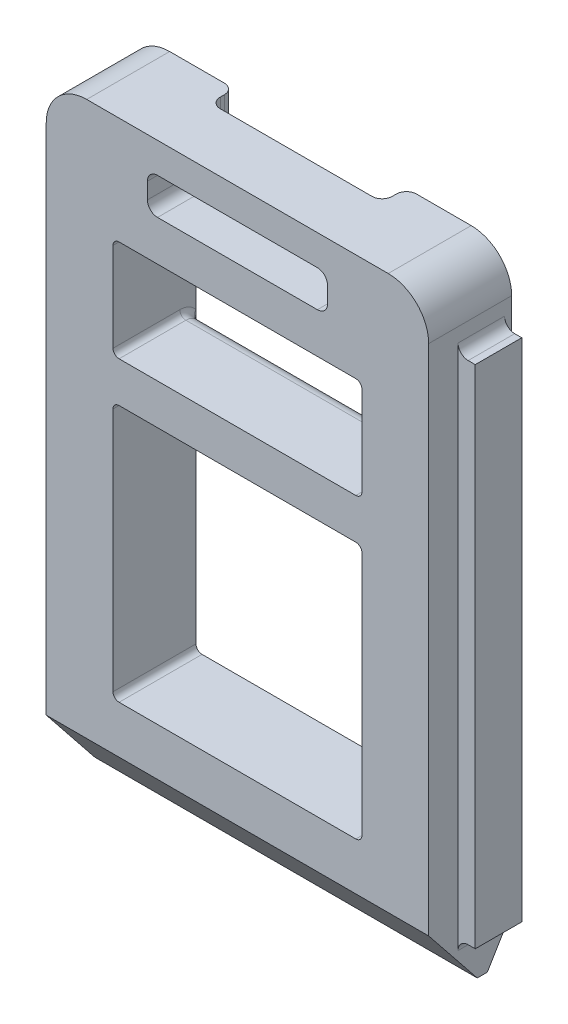
SolidWorks part; units mm, degrees
ref_plane "Front Plane" through (0, 0, 0) normal (0, 0, 1) x (1, 0, 0)
ref_plane "Top Plane" through (0, 0, 0) normal (0, 1, 0) x (1, 0, 0)
ref_plane "Right Plane" through (0, 0, 0) normal (1, 0, 0) x (0, 0, -1)
sketch "Sketch1" plane through (0, 0, 110.6411) normal (0, 0, 1) x (1, 0, 0)
  line L0 (16.3491, 91.493) -> (16.3491, 66.493) construction
  line L1 (16.1491, 94.693) -> (-2.7509, 94.693)
  line L2 (16.1491, 94.693) -> (16.1491, 64.343)
  line L3 (16.1491, 64.343) -> (-2.7509, 64.343)
  line L4 (-2.7509, 94.693) -> (-2.7509, 64.343)
  line L5 (-2.9509, 66.493) -> (-2.9509, 91.493) construction
  line L6 (16.3491, 91.493) -> (-2.9509, 91.493) construction
  line L7 (16.3491, 66.493) -> (18.9491, 66.493) construction
  dimension "D1" = 0.2
  dimension "D2" = 0.2
  dimension "D3" = 3.2
  dimension "D4" = 2.15
extrude "Boss-Extrude1" add sketch "Sketch1" along normal offset from surface (4.1 mm away) 0.5 from offset 0.4
sketch "Sketch2" plane through (0, 94.693, 0) normal (0, 1, 0) x (1, 0, 0)
  line L0 (-2.7509, -115.1411) -> (-2.7509, -111.0411) construction
  line L1 (16.1491, -115.1411) -> (16.1491, -111.0411) construction
  line L2 (-2.7509, -113.6911) -> (-2.7509, -111.3911)
  line L3 (16.1491, -113.6911) -> (16.1491, -111.3911)
  line L4 (-3.9509, -114.0411) -> (-2.9509, -114.0411) construction
  line L5 (-3.9509, -111.0411) -> (-3.9509, -114.0411) construction
  line L6 (-2.9509, -111.0411) -> (-3.9509, -111.0411) construction
  line L7 (17.3491, -111.0411) -> (16.3491, -111.0411) construction
  line L8 (17.3491, -114.0411) -> (17.3491, -111.0411) construction
  line L9 (16.3491, -114.0411) -> (17.3491, -114.0411) construction
  line L10 (-3.9509, -114.0411) -> (-2.9509, -114.0411) construction
  line L11 (-3.9509, -111.0411) -> (-3.9509, -114.0411) construction
  line L12 (-2.9509, -111.0411) -> (-3.9509, -111.0411) construction
  line L13 (17.3491, -111.0411) -> (16.3491, -111.0411) construction
  line L14 (17.3491, -114.0411) -> (17.3491, -111.0411) construction
  line L15 (16.3491, -114.0411) -> (17.3491, -114.0411) construction
  line L16 (16.1491, -113.6911) -> (16.9991, -113.6911)
  line L17 (16.9991, -113.6911) -> (16.9991, -111.3911)
  line L18 (16.9991, -111.3911) -> (16.1491, -111.3911)
  line L19 (-2.7509, -111.3911) -> (-3.6009, -111.3911)
  line L20 (-3.6009, -111.3911) -> (-3.6009, -113.6911)
  line L21 (-3.6009, -113.6911) -> (-2.7509, -113.6911)
  line L22 (16.3491, -113.6911) -> (16.9991, -113.6911) construction
  line L23 (16.9991, -111.3911) -> (16.3491, -111.3911) construction
  line L24 (-3.6009, -113.6911) -> (-2.9509, -113.6911) construction
  line L25 (-2.9509, -111.3911) -> (-3.6009, -111.3911) construction
  dimension "D1" = 0.35
extrude "Boss-Extrude2" add sketch "Sketch2" against normal up to surface (25 mm away) from surface at -3.2
fillet "Fillet3" radius 2 2 edges at (-2.7509, 94.693, 113.0911) (16.1491, 94.693, 113.0911)
sketch "Sketch3" plane through (0, 0, 115.1411) normal (0, 0, 1) x (1, 0, 0)
  line L0 (14.1491, 94.693) -> (-0.7509, 94.693) construction
  line L1 (11.1491, 93.193) -> (2.2491, 93.193)
  line L2 (11.1491, 93.193) -> (11.1491, 91.393)
  line L3 (11.1491, 91.393) -> (2.2491, 91.393)
  line L4 (2.2491, 93.193) -> (2.2491, 91.393)
  line L5 (16.1491, 64.343) -> (16.1491, 92.693) construction
  line L6 (-2.7509, 92.693) -> (-2.7509, 64.343) construction
  dimension "D1" = 1.5
  dimension "D2" = 1.8
  dimension "D3" = 5
  dimension "D4" = 5
extrude "Cut-Extrude1" cut sketch "Sketch3" against normal up to next
fillet "Fillet4" radius 0.5 4 edges at (2.2491, 91.393, 113.0911) (2.2491, 93.193, 113.0911) (11.1491, 91.393, 113.0911) (11.1491, 93.193, 113.0911)
sketch "Sketch4" plane through (-2.7509, 0, 0) normal (-1, 0, 0) x (0, 0, 1)
  line L0 (111.0411, 66.343) -> (112.2411, 64.343)
  line L1 (111.0411, 92.693) -> (111.0411, 64.343) construction
  line L2 (115.1411, 64.343) -> (111.0411, 64.343) construction
  line L3 (112.2411, 64.343) -> (112.7411, 64.343) construction
  line L4 (112.7411, 64.343) -> (115.1411, 67.343)
  line L5 (115.1411, 92.693) -> (115.1411, 64.343) construction
  line L6 (115.1411, 67.343) -> (115.1411, 64.343)
  line L7 (115.1411, 64.343) -> (112.7411, 64.343)
  line L8 (112.2411, 64.343) -> (111.0411, 64.343)
  line L9 (111.0411, 64.343) -> (111.0411, 66.343)
  dimension "D1" = 0.5
  dimension "D2" = 2
  dimension "D3" = 2.4
  dimension "D4" = 3
extrude "Cut-Extrude2" cut sketch "Sketch4" against normal up to next
sketch "Sketch5" plane through (0, 0, 115.1411) normal (0, 0, 1) x (1, 0, 0)
  line L0 (2.7491, 91.393) -> (10.6491, 91.393) construction
  line L1 (12.8491, 89.393) -> (0.5491, 89.393)
  line L2 (12.8491, 89.393) -> (12.8491, 69.693)
  line L3 (12.8491, 69.693) -> (0.5491, 69.693)
  line L4 (0.5491, 89.393) -> (0.5491, 69.693)
  line L5 (16.3491, 66.493) -> (18.9491, 66.493) construction
  line L6 (16.3491, 90.693) -> (16.3491, 67.293) construction
  line L7 (-2.9509, 67.293) -> (-2.9509, 90.693) construction
  dimension "D1" = 2
  dimension "D2" = 3.2
  dimension "D3" = 3.5
  dimension "D4" = 3.5
extrude "Cut-Extrude3" cut sketch "Sketch5" against normal up to next
fillet "Fillet5" radius 0.5 4 edges at (16.1491, 66.493, 112.5411) (16.1491, 91.493, 112.5411) (-2.7509, 91.493, 112.5411) (-2.7509, 66.493, 112.5411)
sketch "Sketch6" plane through (0, 94.693, 0) normal (0, 1, 0) x (1, 0, 0)
  line L0 (14.1491, -111.0411) -> (-0.7509, -111.0411) construction
  line L1 (10.9491, -111.0411) -> (2.4491, -111.0411)
  line L2 (10.9491, -111.0411) -> (10.9491, -112.2411)
  line L3 (10.9491, -112.2411) -> (2.4491, -112.2411)
  line L4 (2.4491, -111.0411) -> (2.4491, -112.2411)
  line L5 (14.1491, -115.1411) -> (-0.7509, -115.1411) construction
  point P6 (6.6991, -112.2411)
  point P9 (6.6991, -115.1411)
  dimension "D1" = 8.5
  dimension "D2" = 1.2
extrude "Cut-Extrude4" cut sketch "Sketch6" against normal up to surface (5.3 mm away) up to face at (6.6991, 89.393, 113.0911)
sketch "Sketch7" plane through (0, 0, 115.1411) normal (0, 0, 1) x (1, 0, 0)
  line L0 (12.8491, 69.693) -> (12.8491, 89.393) construction
  line L1 (12.8491, 84.393) -> (0.5491, 84.393)
  line L2 (12.8491, 84.393) -> (12.8491, 82.393)
  line L3 (12.8491, 82.393) -> (0.5491, 82.393)
  line L4 (0.5491, 84.393) -> (0.5491, 82.393)
  line L5 (0.5491, 89.393) -> (0.5491, 69.693) construction
  line L6 (12.8491, 89.393) -> (0.5491, 89.393) construction
  dimension "D1" = 2
  dimension "D2" = 5
extrude "Boss-Extrude3" add sketch "Sketch7" against normal offset from surface (4 mm away) 0.5
fillet "Fillet6" radius 0.7 2 edges at (6.6991, 82.393, 111.1411) (6.6991, 84.393, 111.1411)
fillet "Fillet7" radius 0.5 6 edges at (2.4491, 93.893, 112.2411) (2.4491, 90.443, 111.0411) (2.4491, 90.443, 112.2411) (10.9491, 90.443, 112.2411) (10.9491, 93.893, 112.2411) (10.9491, 93.893, 111.0411)
fillet "Fillet8" radius 0.3 12 edges at (0.5491, 82.393, 113.4911) (0.5491, 82.5981, 111.3461) (0.5491, 84.188, 111.3461) (12.8491, 82.393, 113.4911) (12.8491, 82.5981, 111.3461) (12.8491, 84.188, 111.3461) (0.5491, 69.693, 113.0911) (0.5491, 89.393, 113.0911) (12.8491, 89.393, 113.0911) (12.8491, 69.693, 113.0911) (0.5491, 84.393, 113.4911) (12.8491, 84.393, 113.4911)
